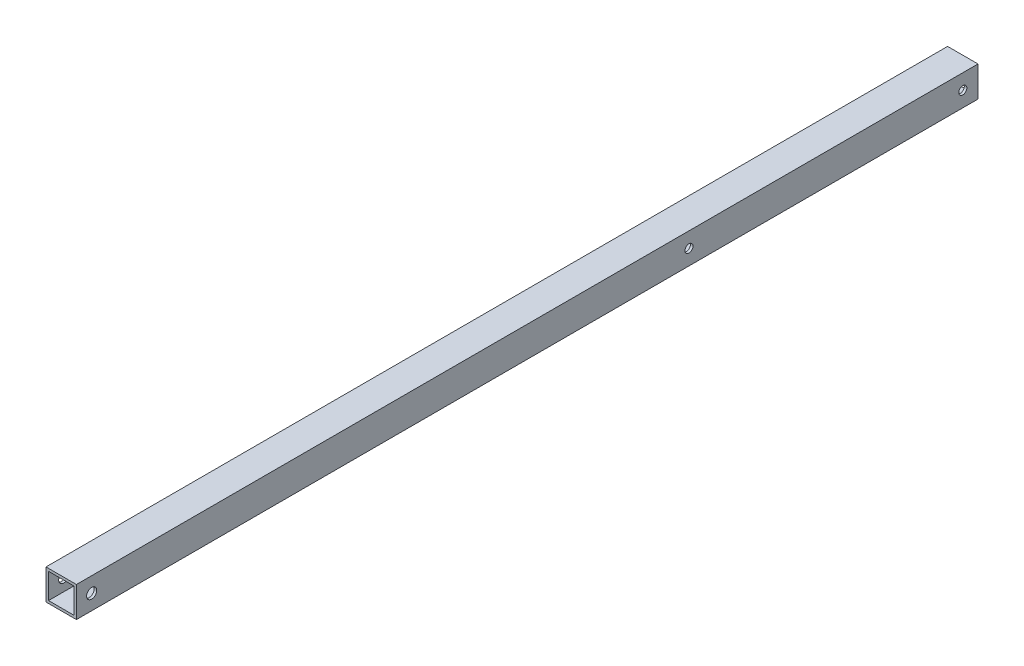
SolidWorks part; units mm, degrees
material "Plain Carbon Steel"
ref_plane "Front Plane" through (0, 0, 0) normal (0, 0, 1) x (1, 0, 0)
ref_plane "Top Plane" through (0, 0, 0) normal (0, 1, 0) x (1, 0, 0)
ref_plane "Right Plane" through (0, 0, 0) normal (1, 0, 0) x (0, 0, -1)
sketch "Sketch2" plane through (0, 0, 0) normal (0, 0, 1) x (1, 0, 0)
  line L0 (0, 19.05) -> (3.175, 19.05) construction
  line L1 (0, 0) -> (38.1, 0)
  line L2 (0, 0) -> (0, 38.1)
  line L3 (0, 38.1) -> (38.1, 38.1)
  line L4 (38.1, 0) -> (38.1, 38.1)
  line L5 (3.175, 3.175) -> (34.925, 3.175)
  line L6 (3.175, 3.175) -> (3.175, 34.925)
  line L7 (3.175, 34.925) -> (34.925, 34.925)
  line L8 (34.925, 3.175) -> (34.925, 34.925)
  line L9 (19.05, 34.925) -> (19.05, 38.1) construction
  line L10 (34.925, 19.05) -> (38.1, 19.05) construction
  line L11 (19.05, 0) -> (19.05, 3.175) construction
  dimension "D1" = 38.1
  dimension "D2" = 3.175
  dimension "D3" = 38.1
extrude "Boss-Extrude1" add sketch "Sketch2" along normal blind 1129.03
hole_wizard "X (0.397) Diameter Hole1" positions "Sketch4" profile "Sketch3" hole size "X" standard "ANSI Inch" end condition through all
sketch "Sketch4" plane through (0, 0, 0) normal (-1, 0, 0) x (0, 0, 1)
  line L0 (0, 19.05) -> (19.05, 19.05) construction
  line L1 (0, 38.1) -> (0, 0) construction
  line L2 (19.05, 19.05) -> (361.95, 19.05) construction
  point P0 (19.05, 19.05)
  point P2 (361.95, 19.05)
  dimension "D1" = 19.05
  dimension "D2" = 342.9
sketch "Sketch3" plane through (0, 19.05, 19.05) normal (0, 1, 0) x (0, 0, 1)
  line L0 (0, 0) -> (0, 38.1)
  line L1 (0, 38.1) -> (5.0419, 38.1)
  line L2 (5.0419, 38.1) -> (5.0419, 0)
  line L5 (5.0419, 0) -> (0, 0)
  line L11 (0, -6.35) -> (0, 107.95) construction
  dimension "Thru Hole Dia." = 10.0838
  dimension "Thru Hole Depth" = 38.1
hole_wizard "1/2 (0.5) Diameter Hole1" positions "Sketch6" profile "Sketch5" hole size "1/2" standard "ANSI Inch" end condition through all
sketch "Sketch6" plane through (0, 0, 0) normal (-1, 0, 0) x (0, 0, 1)
  line L0 (1129.03, 38.1) -> (1129.03, 0) construction
  line L1 (1129.03, 0) -> (0, 0) construction
  point P0 (1109.98, 19.05)
  dimension "D1" = 19.05
  dimension "D2" = 19.05
sketch "Sketch5" plane through (0, 19.05, 1109.98) normal (0, 1, 0) x (0, 0, 1)
  line L0 (0, 0) -> (0, 38.1)
  line L1 (0, 38.1) -> (6.35, 38.1)
  line L2 (6.35, 38.1) -> (6.35, 0)
  line L5 (6.35, 0) -> (0, 0)
  line L11 (0, -6.35) -> (0, 107.95) construction
  dimension "Thru Hole Dia." = 12.7
  dimension "Thru Hole Depth" = 38.1
equation "\"49inin\"=47"
